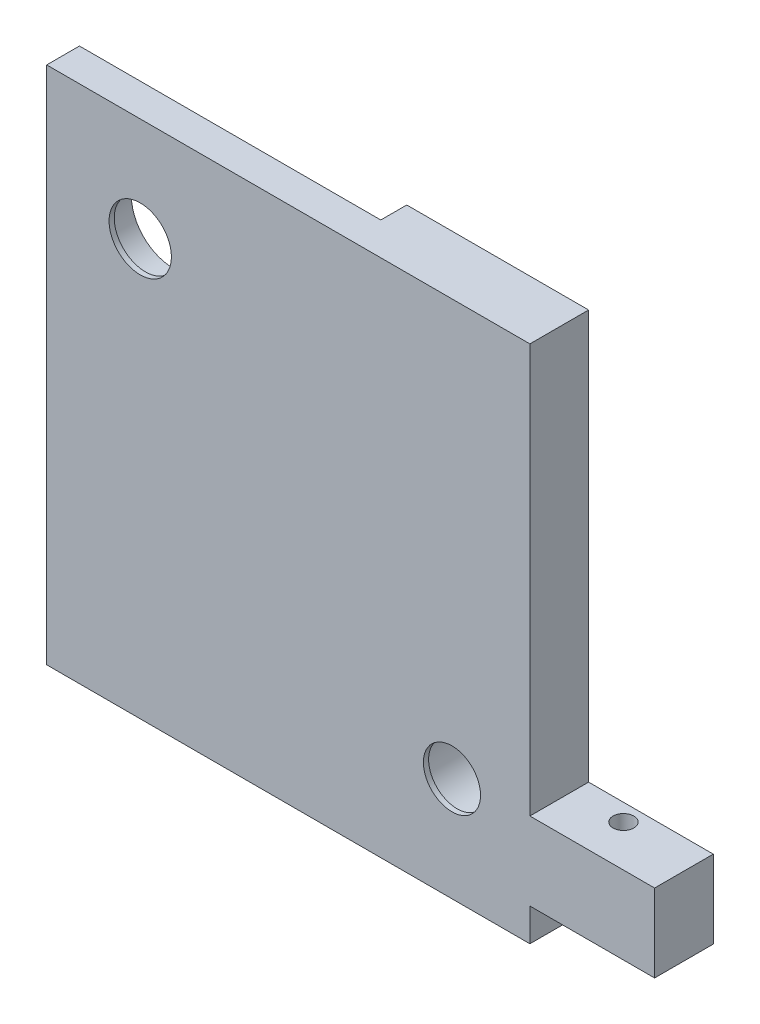
SolidWorks part; units mm, degrees
ref_plane "Front Plane" through (0, 0, 0) normal (0, 0, 1) x (1, 0, 0)
ref_plane "Top Plane" through (0, 0, 0) normal (0, 1, 0) x (1, 0, 0)
ref_plane "Right Plane" through (0, 0, 0) normal (1, 0, 0) x (0, 0, -1)
sketch "Sketch1" plane through (0, 0, 0) normal (0, 0, 1) x (1, 0, 0)
  line L1 (-76.1871, 64.9281) -> (16.8129, 64.9281)
  line L2 (-76.1871, 64.9281) -> (-76.1871, -35.0719)
  line L3 (-76.1871, -35.0719) -> (16.8129, -35.0719)
  line L4 (16.8129, 64.9281) -> (16.8129, -35.0719)
  dimension "D1" = 93
  dimension "D2" = 100
extrude "Boss-Extrude2" add sketch "Sketch1" along normal blind 6.3 contours L1 L4 L3 L2
sketch "Sketch3" plane through (0, 0, 0) normal (0, 0, -1) x (-1, 0, 0)
  line L0 (76.1871, -35.0719) -> (-16.8129, -35.0719) construction
  line L1 (-16.8129, 64.9281) -> (18.1871, 64.9281)
  line L2 (-16.8129, 64.9281) -> (-16.8129, -35.0719)
  line L3 (-16.8129, -35.0719) -> (18.1871, -35.0719)
  line L4 (18.1871, 64.9281) -> (18.1871, -35.0719)
  line L5 (-16.8129, 64.9281) -> (-16.8129, -35.0719) construction
  dimension "D1" = 0
  dimension "D2" = 0
  dimension "D3" = 35
  dimension "D4" = 100
extrude "Boss-Extrude3" add sketch "Sketch3" along normal blind 5
sketch "Sketch4" plane through (16.8129, 0, 0) normal (1, 0, 0) x (0, 0, -1)
  line L0 (-6.3, 64.9281) -> (-6.3, -35.0719) construction
  line L1 (-6.3, -13.7719) -> (5, -13.7719)
  line L2 (-6.3, -13.7719) -> (-6.3, -28.7719)
  line L3 (-6.3, -28.7719) -> (5, -28.7719)
  line L4 (5, -13.7719) -> (5, -28.7719)
  line L5 (5, 64.9281) -> (5, -35.0719) construction
  line L6 (-6.3, -35.0719) -> (5, -35.0719) construction
  dimension "D1" = 6.3
  dimension "D2" = 15
extrude "Boss-Extrude4" add sketch "Sketch4" along normal blind 24
sketch "Sketch5" plane through (0, -13.7719, 0) normal (0, 1, 0) x (1, 0, 0)
  line L0 (40.8129, -6.3) -> (16.8129, -6.3) construction
  line L2 (16.8129, 5) -> (16.8129, -6.3) construction
  circle A0 centre (26.8129, 1.7) radius 2
  dimension "D2" = 4
  dimension "D3" = 10
  dimension "D1" = 8
extrude "Cut-Extrude1" cut sketch "Sketch5" against normal blind 50
sketch "Sketch6" plane through (0, 0, -5) normal (0, 0, -1) x (-1, 0, 0)
  line L0 (-16.8129, -35.0719) -> (18.1871, -35.0719) construction
  line L1 (-16.8129, -28.7719) -> (-16.8129, -35.0719) construction
  circle A0 centre (-1.8129, -15.0719) radius 7.5
  dimension "D1" = 15
  dimension "D2" = 20
  dimension "D3" = 15
extrude "Cut-Extrude2" cut sketch "Sketch6" against normal blind 50
sketch "Sketch7" plane through (0, 0, 0) normal (0, 0, -1) x (-1, 0, 0)
  line L0 (76.1871, -35.0719) -> (18.1871, -35.0719) construction
  line L2 (-16.8129, 64.9281) -> (-16.8129, -13.7719) construction
  circle A0 centre (58.1871, 44.9281) radius 8
  dimension "D1" = 16
  dimension "D2" = 80
  dimension "D3" = 75
extrude "Cut-Extrude3" cut sketch "Sketch7" against normal blind 50
extrude "Extrude-Thin1" add sketch "Sketch7<2>" along normal blind 1 from surface thin starting at face at (-50.1871, 44.9281, 6.3) thin type one direction reverse wall 2
sketch "Sketch7<2>" plane through (0, 0, 0) normal (0, 0, -1) x (-1, 0, 0) same geometry as "Sketch7"
extrude "Extrude-Thin2" add sketch "Sketch6<2>" along normal blind 1 from surface thin starting at face at (9.3129, -15.0719, 6.3) thin type one direction reverse wall 2
sketch "Sketch6<2>" plane through (0, 0, -5) normal (0, 0, -1) x (-1, 0, 0) same geometry as "Sketch6"
